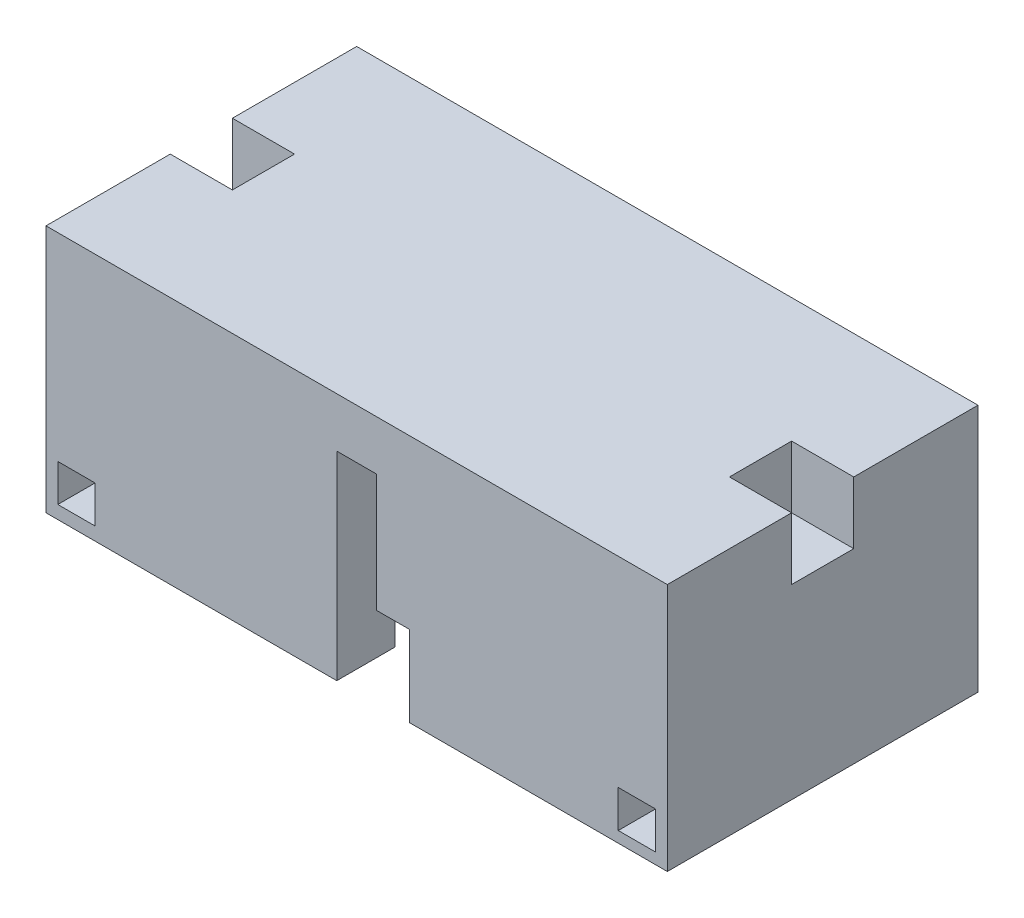
SolidWorks part; units mm, degrees
note: The reader was unsure of these and kept them because the rebuilt part matched: shared geometry of "Sketch34<3>", "Sketch34<4>".
ref_plane "Front Plane" through (0, 0, 0) normal (0, 0, 1) x (1, 0, 0)
ref_plane "Top Plane" through (0, 0, 0) normal (0, 1, 0) x (1, 0, 0)
ref_plane "Right Plane" through (0, 0, 0) normal (1, 0, 0) x (0, 0, -1)
sketch "Sketch1" plane through (0, 0, 0) normal (0, 1, 0) x (1, 0, 0)
  line L1 (-50, 50) -> (50, 50)
  line L2 (-50, 50) -> (-50, -50)
  line L3 (-50, -50) -> (50, -50)
  line L4 (50, 50) -> (50, -50)
  line L5 (-50, 50) -> (50, -50) construction
  line L6 (-50, -50) -> (50, 50) construction
  point P0 (0, 0)
  dimension "D1" = 100
  dimension "D2" = 100
extrude "Boss-Extrude1" add sketch "Sketch1" against normal blind 50
sketch "Sketch2" plane through (0, 0, 0) normal (0, 1, 0) x (1, 0, 0)
  line L0 (-50, -50) -> (50, -50)
  line L1 (50, -50) -> (50, 50)
  line L2 (50, 50) -> (-50, 50)
  line L3 (-50, 50) -> (-50, -50)
  line L4 (0, -50) -> (0, 0)
  line L5 (0, 0) -> (-50, 0)
  line L6 (0, 0) -> (50, 0)
  line L7 (-50, 0) -> (-50, -50)
  line L8 (50, 0) -> (50, -50)
  line L9 (-50, 0) -> (-50, 50)
  line L10 (50, 0) -> (50, 50)
  line L11 (0, 0) -> (0, 50)
ref_plane "BACK" through (0, -50, 0) normal (0, -1, 0) x (-1, 0, 0)
sketch "Sketch3" plane through (0, -50, 0) normal (0, -1, 0) x (-1, 0, 0)
  line L0 (-50, 50) -> (50, 50)
  line L1 (50, 50) -> (50, -50)
  line L2 (50, -50) -> (-50, -50)
  line L3 (-50, -50) -> (-50, 50)
  line L12 (-5, -20) -> (5, -20)
  line L13 (-5, -20) -> (-5, -30)
  line L14 (-5, -30) -> (5, -30)
  line L15 (5, -20) -> (5, -30)
  dimension "D1" = 10
  dimension "D2" = 10
sketch "Sketch4" plane through (0, 0, 0) normal (0, 1, 0) x (1, 0, 0)
  line L0 (0, -40) -> (0, -20)
  line L1 (5, -20) -> (-5, -20) construction
  circle A0 centre (0, 0) radius 40
  dimension "D1" = 80
ref_plane "Plane2" through (0, 0, 50) normal (0, 0, 1) x (1, 0, 0)
sketch "Sketch6" plane through (0, 0, 50) normal (0, 0, 1) x (1, 0, 0)
  line L0 (-50, 0) -> (-50, -150)
  line L1 (-50, 0) -> (50, 0)
  line L2 (50, 0) -> (50, -150)
  line L3 (50, -150) -> (-50, -150)
  line L4 (-50, -50) -> (50, -50)
  circle A0 centre (0, -150) radius 100
  dimension "D1" = 150
extrude "Boss-Extrude4" add sketch "Sketch6" against normal blind 50 separate body contours A0 L4 L0 | A0 L2 L4
ref_plane "Plane4" through (0, -63.3975, 0) normal (0, -1, 0) x (-1, 0, 0)
ref_plane "Plane5" through (0, 0, 0) normal (0, 0, -1) x (-1, 0, 0)
sketch "Sketch10" plane through (0, 0, 0) normal (0, 0, -1) x (-1, 0, 0)
  line L0 (50, -50) -> (50, -70)
  line L1 (50, -50) -> (-50, -50) construction
  line L2 (50, -50) -> (50, -63.3975) construction
  line L3 (50, -50) -> (30, -50)
  line L4 (-50, -50) -> (50, -50) construction
  line L5 (50, -70) -> (30, -50)
  line L6 (-68.5695, -50) -> (-48.5695, -50)
  line L7 (-55, -50) -> (55, -50) construction
  line L8 (-68.5695, -50) -> (-50, -57.4278)
  line L9 (-50, -50) -> (-50, -63.3975) construction
  line L10 (-48.5695, -50) -> (-50, -57.4278)
  dimension "D1" = 20
  dimension "D2" = 20
  dimension "D3" = 20
  dimension "D4" = 20
sketch "Sketch11" plane through (0, -63.3975, 0) normal (0, -1, 0) x (-1, 0, 0)
  line L0 (-50, -50) -> (-50, 0)
  line L1 (-50, 0) -> (50, 0)
  line L2 (50, 50) -> (50, -50) construction
  line L3 (50, 0) -> (50, -50)
  line L4 (50, -50) -> (-50, -50)
extrude "Cut-Extrude4" cut sketch "Sketch11" against normal blind 100
sketch "Sketch12" plane through (0, 0, 50) normal (0, 0, 1) x (1, 0, 0)
  line L0 (-50, -50) -> (-50, -30)
  line L1 (-50, -50) -> (-50, 0) construction
  line L2 (-50, -30) -> (-30, -30)
  line L3 (-30, -30) -> (-50, -50)
  line L4 (50, -50) -> (50, -30)
  line L5 (50, -50) -> (50, 0) construction
  line L6 (50, -30) -> (30, -30)
  line L7 (30, -30) -> (50, -50)
  dimension "D1" = 20
  dimension "D2" = 20
  dimension "D3" = 20
ref_plane "Plane6" through (0, 0, -50) normal (0, 0, -1) x (-1, 0, 0)
sketch "Sketch13" plane through (0, 0, -50) normal (0, 0, -1) x (-1, 0, 0)
  line L2 (50, -50) -> (50, -40)
  line L3 (50, -50) -> (50, -30) construction
  line L4 (50, -40) -> (-50, -40)
  line L5 (-50, -50) -> (-50, -30) construction
  line L6 (-50, -40) -> (-50, -50)
  line L7 (-50, -50) -> (50, -50)
extrude "Cut-Extrude5" cut sketch "Sketch13" against normal blind 50
sketch "Sketch14" plane through (0, -50, 0) normal (0, -1, 0) x (-1, 0, 0)
  line L0 (0, -50) -> (0, 0) construction
  line L1 (-5, -20) -> (5, -20)
  line L2 (-5, -20) -> (-5, -30)
  line L3 (-5, -30) -> (5, -30)
  line L4 (5, -20) -> (5, -30)
  line L5 (-5, -20) -> (5, -30) construction
  line L6 (-5, -30) -> (5, -20) construction
  line L8 (-4, -21) -> (4, -21)
  line L9 (-4, -21) -> (-4, -29)
  line L10 (-4, -29) -> (4, -29)
  line L11 (4, -21) -> (4, -29)
  line L12 (-4, -21) -> (4, -29) construction
  line L13 (-4, -29) -> (4, -21) construction
  point P0 (0, -25)
  point P8 (0, -25)
  dimension "D1" = 8
  dimension "D2" = 8
extrude "Cut-Extrude6" cut sketch "Sketch2" against normal blind 25 contours L5 L7 L0 L4 | L8 L6 L4 L0
sketch "Sketch18" plane through (0, 0, 0) normal (0, 0, -1) x (-1, 0, 0)
  line L0 (50, -50) -> (50, -70)
  line L1 (50, -70) -> (30, -50)
  line L2 (30, -50) -> (50, -50)
  line L3 (-50, -50) -> (-50, -69.5)
  line L4 (-50, -69.5) -> (-30.5, -50)
  line L5 (-50, -50) -> (50, -50) construction
  line L6 (-30.5, -50) -> (-50, -50)
  dimension "D1" = 45
extrude "Boss-Extrude5" add sketch "Sketch18" against normal blind 19.5
sketch "Sketch20" plane through (0, -40, 0) normal (0, -1, 0) x (1, 0, 0)
  line L0 (0, 0) -> (-30, 0)
  line L1 (-60.3987, 0) -> (60.3987, 0) construction
  line L2 (-30, 0) -> (-30, -22.9)
  line L3 (-30, -22.9) -> (-14, -22.9)
  line L4 (-14, -22.9) -> (-14, -27.9)
  line L5 (-14, -27.9) -> (-11.1, -27.9)
  line L6 (-11.1, -27.9) -> (-11.1, -22.9)
  line L7 (-30, -22.9) -> (-14, -22.9)
  line L8 (-7, -22.9) -> (-7, -14.9)
  line L9 (-7, -14.9) -> (-2.8, -14.9)
  line L10 (-2.8, -14.9) -> (3.2, -14.9)
  line L11 (3.2, -14.9) -> (3.2, 0)
  line L12 (3.2, 0) -> (0, 0)
  line L13 (-11.1, -22.9) -> (-7, -22.9)
  line L14 (3.2, 0) -> (-30, 0)
  line M4 (50, 0) -> (-50, 0)
extrude "Cut-Extrude7" cut sketch "Sketch20" against normal blind 12 contours L6 L13 L8 L9 L10 L11 L2 L3 L4 L5 M4
sketch "Sketch21" plane through (0, -40, 0) normal (0, -1, 0) x (1, 0, 0)
  line L0 (0, 0) -> (-3.2, 0)
  line L1 (-60.3987, 0) -> (60.3987, 0) construction
  line L2 (-3.2, 0) -> (-3.2, -14.9)
  line L3 (-7, -14.9) -> (3.2, -14.9) construction
  line L4 (-3.2, -14.9) -> (3.2, -14.9)
  line L5 (3.2, -14.9) -> (3.2, 0)
  line L6 (3.2, -14.9) -> (3.2, 0) construction
  line L7 (3.2, 0) -> (-3.2, 0)
  line M8 (3.2, 0) -> (3.2, -14.9)
  line M9 (3.2, -14.9) -> (-7, -14.9)
extrude "Cut-Extrude8" cut sketch "Sketch21" against normal blind 32 contours L7 L0 L2 M8 M9
ref_plane "Plane7" through (0, 0, 0) normal (0, 0, -1) x (-1, 0, 0)
sketch "Sketch27" plane through (0, 0, 0) normal (0, 0, -1) x (-1, 0, 0)
  line L0 (-5, -50) -> (-5, -40)
  line L1 (-5, -50) -> (5, -50) construction
  line L2 (50, -40) -> (-50, -40) construction
  line L3 (-5, -40) -> (-3.2, -40)
  line L4 (-3.2, -50) -> (-3.2, -18)
  line L5 (-3.2, -18) -> (3.2, -18)
  line L6 (3.2, -18) -> (3.2, -50)
  line L7 (3.2, -50) -> (-3.2, -50)
extrude "Cut-Extrude9" cut sketch "Sketch27" against normal blind 29 contours L7 L6 L5 L4
sketch "Sketch28" plane through (0, -25, 0) normal (0, 1, 0) x (1, 0, 0)
  line L0 (0, -25) -> (0, -10)
  line L1 (-7.5, -17.5) -> (7.5, -17.5)
  line L2 (-7.5, -17.5) -> (-7.5, -32.5)
  line L3 (-7.5, -32.5) -> (7.5, -32.5)
  line L4 (7.5, -17.5) -> (7.5, -32.5)
  line L5 (-7.5, -17.5) -> (7.5, -32.5) construction
  line L6 (-7.5, -32.5) -> (7.5, -17.5) construction
  point P0 (0, -25)
  dimension "D1" = 15
  dimension "D2" = 15
sketch "Sketch29" plane through (0, 0, -50) normal (0, 0, -1) x (-1, 0, 0)
  line L0 (0, -40) -> (30, -40)
  line L1 (50, -40) -> (-50, -40) construction
  line L2 (30, -40) -> (30, -28)
  line L3 (30, -28) -> (0, -28)
  line L4 (0, -28) -> (0, -40)
  line L5 (24, -36.5) -> (24, -40)
  line L6 (24, -34) -> (24, -36.5)
  line L7 (24, -34) -> (24, -31.5)
  line L8 (24, -31.5) -> (30, -31.5)
  line L9 (24, -36.5) -> (30, -36.5)
  line L10 (24, -40) -> (30, -40)
  line L11 (30, -36.5) -> (24, -36.5)
extrude "Cut-Extrude10" cut sketch "Sketch29" against normal blind 28 contours L6 L9 L2 L8 L7 | L9 L5 L0 L2
sketch "Sketch30" plane through (0, -25, 0) normal (0, 1, 0) x (1, 0, 0)
  line L0 (-50, -50) -> (-50, 0)
  line L1 (-50, 50) -> (-50, -50) construction
  line L2 (-50, 0) -> (50, 0)
  line L3 (50, -50) -> (50, 50) construction
  line L4 (50, 0) -> (50, -50)
  line L5 (50, -50) -> (-50, -50)
sketch "Sketch31" plane through (-50, 0, 0) normal (-1, 0, 0) x (0, 0, 1)
  line L0 (0, -50) -> (0, -40)
  line L1 (-50, -50) -> (50, -50) construction
  line L2 (0, 60.3987) -> (0, -60.3987) construction
  line L3 (0, 36.7438) -> (0, -36.7438) construction
extrude "Cut-Extrude11" cut sketch "Sketch30" against normal blind 45
sketch "Sketch32" plane through (0, 0, 0) normal (0, 0, 1) x (1, 0, 0)
  line L0 (-50, -40) -> (-50, -30.2)
  line L1 (-50, -50) -> (-50, -30) construction
  line L2 (-50, -40) -> (-50, 0) construction
  line L3 (-50, -30.2) -> (-40.2, -30.2)
  line L4 (-40.2, -30.2) -> (-40.2, -40)
  line L5 (-50, -40) -> (-30, -40) construction
  line L6 (-40.2, -40) -> (-50, -40)
  line L7 (50, -40) -> (50, -30.2)
  line L8 (50, -50) -> (50, -30) construction
  line L9 (50, -40) -> (50, 0) construction
  line L10 (50, -30.2) -> (40.2, -30.2)
  line L11 (40.2, -30.2) -> (40.2, -40)
  line L12 (3.2, -40) -> (50, -40) construction
  line L13 (40.2, -40) -> (50, -40)
extrude "Boss-Extrude6" add sketch "Sketch32" along normal blind 9.8
chamfer "Chamfer1" distance 1 angle 45 6 edges at (40.2, -35.1, 9.8) (40.2, -30.2, 4.9) (-40.2, -35.1, 9.8) (-40.2, -30.2, 4.9) (40.2, -40, 4.9) (-40.2, -40, 4.9)
sketch "Sketch34" plane through (0, -40, 0) normal (0, -1, 0) x (1, 0, 0)
  line L0 (-11.1, -27.9) -> (-11.1, -22.9)
  line L1 (-11.1, -22.9) -> (-7, -22.9)
  line L2 (-7, -22.9) -> (-7, -14.9)
  line L3 (-7, -14.9) -> (3.2, -14.9)
  line L4 (3.2, -14.9) -> (3.2, 0)
  line L5 (-60.3987, 0) -> (60.3987, 0) construction
  line L6 (3.2, 0) -> (3.2, -14.9) construction
  line L7 (3.2, 0) -> (-30, 0)
  line L8 (-30, 0) -> (-30, -50) construction
  line L9 (-50, 0) -> (-30, 0) construction
  line L10 (-30, 0) -> (-30, -22.9)
  line L11 (-30, -22.9) -> (-14, -22.9)
  line L12 (-14, -22.9) -> (-14, -27.9)
  line L13 (-14, -27.9) -> (-11.1, -27.9)
  line L14 (-30, 0) -> (-30.5, 0)
  line L15 (-30.5, 0) -> (-30.5, -22.9)
  line L16 (-30, -22.9) -> (-30.5, -22.9)
  line L17 (-30.5, -22.9) -> (-30.5, -33.4)
  line L18 (-30.5, -33.4) -> (-14.5, -33.4)
  line L19 (-14.5, -33.4) -> (-14.5, -38.9)
  line L20 (-14.5, -38.9) -> (-10.6, -38.9)
  line L21 (-10.6, -38.9) -> (-10.6, -33.4)
  line L22 (-10.6, -33.4) -> (-6.5, -33.4)
  line L23 (-6.5, -33.4) -> (-6.5, -24.9)
  line L24 (-6.5, -24.9) -> (8.5, -24.9)
  line L25 (-30.5, -33.4) -> (-30.5, -9.4)
  line L26 (-30.5, -9.4) -> (-14.5, -9.4)
  line L27 (-14.5, -9.4) -> (-14.5, -3.9)
  line L28 (-14.5, -3.9) -> (-10.6, -3.9)
  line L29 (-10.6, -3.9) -> (-10.6, -9.4)
  line L30 (-10.6, -9.4) -> (-3.2, -9.4)
  line L31 (-3.2, 0) -> (-3.2, -14.9) construction
  line L32 (8.5, -24.9) -> (8.5, 0)
  line L33 (8.5, 0) -> (3.2, 0)
  line L34 (3.2, -24.9) -> (3.2, 0)
  line L35 (3.2, 0) -> (8.5, 0)
  line L36 (3.2, -24.9) -> (8.5, -24.9)
  line L37 (-3.2, -9.4) -> (3.2, -9.4)
  line L38 (3.2, -9.4) -> (3.2, -24.9)
  line L39 (-3.2, -9.4) -> (-3.2, 0)
  line L40 (3.2, -24.9) -> (3.2, -33.4)
  line L41 (3.2, -33.4) -> (-6.5, -33.4)
  line L42 (-30.5, -33.4) -> (-30.5, -50)
  line L43 (50, -50) -> (-50, -50) construction
  line L44 (-30.5, -50) -> (-30, -50)
  line L45 (-30, 0) -> (-30, -50) construction
  line L46 (-30, -50) -> (-30, -33.4)
  line L47 (-30, -22.9) -> (-30, -50) construction
  line L48 (-30, -50) -> (-24, -50)
  line L49 (-24, -22.9) -> (-24, -50) construction
  line L50 (-24, -50) -> (-24, -33.4)
  line L51 (-24, -22.9) -> (-24, -50) construction
  line L52 (8.5, -24.9) -> (8.5, -50)
  line L53 (8.5, -50) -> (3.2, -50)
  line L54 (3.2, -50) -> (3.2, -24.9)
  line M18 (40.2, 0) -> (3.2, 0)
  line M19 (3.2, 0) -> (3.2, -14.9)
  line M20 (3.2, -14.9) -> (-7, -14.9)
  line M21 (-7, -14.9) -> (-7, -22.9)
  line M22 (-7, -22.9) -> (-11.1, -22.9)
  line M23 (-11.1, -22.9) -> (-11.1, -27.9)
  line M24 (-11.1, -27.9) -> (-14, -27.9)
  line M25 (-14, -27.9) -> (-14, -22.9)
  line M26 (-14, -22.9) -> (-24, -22.9)
  line M67 (-24, -22.9) -> (-24, -50)
  line M68 (-24, -50) -> (50, -50)
extrude "Boss-Extrude7" add sketch "Sketch34" against normal blind 13 contours L30 L39 L7 L10 L26 L27 L28 L29
extrude "Cut-Extrude12" cut sketch "Sketch34<3>" against normal blind 13 contours L34 L24 L32 M18 M19 | L37 L30 L29 L28 L27 L26 L10 L11 L34 M26 M25 M24 M23 M22 M21 M20 | L24 L34 L18 L19 L20 L21 L22 L23 M20 M21 M22 M23 M24 M25 M26 M67 | L41 L40 L24 L23 | L17 L18 L11 L16 M67 | L26 L15 L16 L10 | L44 L46 L18 L42 | L46 L48 L18 M67
sketch "Sketch34<3>" plane through (0, -40, 0) normal (0, -1, 0) x (1, 0, 0) same geometry as "Sketch34"
sketch "Sketch36" plane through (0, 0, 0) normal (0, 1, 0) x (1, 0, 0)
  line L0 (50, 50) -> (50, 0)
  line L1 (50, -50) -> (50, 50) construction
  line L2 (-50, 50) -> (-50, 20)
  line L3 (40, 25) -> (40, 30)
  line L4 (40, 25) -> (40, 20)
  line L5 (40, 20) -> (50, 20)
  line L6 (40, 30) -> (50, 30)
  line L7 (-50, 50) -> (-50, -50) construction
  line L8 (-50, 20) -> (-40, 20)
  line L9 (-40, 20) -> (-40, 30)
  line L10 (-40, 30) -> (-50, 30)
  line L11 (-50, 20) -> (-50, 0)
  line L12 (-50, 0) -> (50, 0)
  line L13 (50, 50) -> (-50, 50)
extrude "Cut-Extrude13" cut sketch "Sketch36" against normal blind 10 and the other way through all contours L9 L10 L2 L8 | L6 L3 L4 L5 L0
sketch "Sketch37" plane through (0, -40, 0) normal (0, -1, 0) x (1, 0, 0)
  line L0 (-50, 0) -> (-50, 9.8)
  line L1 (-50, -50) -> (-50, 50) construction
  line L2 (-50, 9.8) -> (-40.2, 9.8)
  line L3 (-40.2, 9.8) -> (-40.2, 0)
  line L4 (-50, 0) -> (-30, 0) construction
  line L5 (-40.2, 0) -> (-50, 0)
  line L6 (50, 0) -> (40.2, 0)
  line L7 (50, 50) -> (50, -50) construction
  line L8 (-60.3987, 0) -> (60.3987, 0) construction
  line L9 (40.2, 8.8) -> (40.2, 0) construction
  line L10 (40.2, 0) -> (40.2, 10.0488)
  line L11 (40.2, 10.0488) -> (50, 10.0488)
  line L12 (50, 10.0488) -> (50, 0)
extrude "Cut-Extrude15" cut sketch "Sketch37" against normal blind 10
sketch "Sketch38" plane through (0, 0, 0) normal (0, 0, 1) x (1, 0, 0)
  line L0 (-50, -40) -> (-40.2, -40)
  line L1 (-50, -40) -> (-3.2, -40) construction
  line L2 (-40.2, -40) -> (-40.2, -30.2)
  line L3 (-40.2, -30.2) -> (-50, -30.2)
  line L4 (-50, -50) -> (-50, -30) construction
  line L5 (-50, -30.2) -> (-50, -40)
  line L6 (-45.1, -40) -> (-45.1, -34.8905)
  line L7 (50, -40) -> (40.2, -40)
  line L8 (-48.1, -31.8905) -> (-42.1, -31.8905)
  line L9 (-48.1, -31.8905) -> (-48.1, -37.8905)
  line L10 (-48.1, -37.8905) -> (-42.1, -37.8905)
  line L11 (-42.1, -31.8905) -> (-42.1, -37.8905)
  line L12 (-48.1, -31.8905) -> (-42.1, -37.8905) construction
  line L13 (-48.1, -37.8905) -> (-42.1, -31.8905) construction
  line L14 (50, -50) -> (50, -30) construction
  line L15 (8.5, -40) -> (50, -40) construction
  line L16 (40.2, -40) -> (40.2, -30.2)
  line L17 (40.2, -30.2) -> (50, -30.2)
  line L18 (50, -30.2) -> (50, -40)
  line L19 (45.1, -40) -> (45.1, -35.2309)
  line L21 (42.1, -32.2309) -> (48.1, -32.2309)
  line L22 (42.1, -32.2309) -> (42.1, -38.2309)
  line L23 (42.1, -38.2309) -> (48.1, -38.2309)
  line L24 (48.1, -32.2309) -> (48.1, -38.2309)
  line L25 (42.1, -32.2309) -> (48.1, -38.2309) construction
  line L26 (42.1, -38.2309) -> (48.1, -32.2309) construction
  dimension "D1" = 6
  dimension "D2" = 6
  dimension "D3" = 6
  dimension "D4" = 6
  dimension "D5" = 9.8
  dimension "D6" = 9.8
  dimension "D7" = 9.8
  dimension "D8" = 9.8
extrude "Cut-Extrude16" cut sketch "Sketch38" against normal blind 6
sketch "Sketch39" plane through (0, -40, 0) normal (0, -1, 0) x (1, 0, 0)
  line L0 (-3.2, -14.9) -> (-3.2, -33.4)
  line L1 (-10.6, -33.4) -> (3.2, -33.4) construction
  line L2 (-3.2, -33.4) -> (3.2, -33.4)
  line L3 (3.2, -33.4) -> (3.2, -14.9)
  line L4 (3.2, -14.9) -> (-3.2, -14.9)
  line L5 (-3.2, -33.4) -> (-3.2, -50)
  line L6 (3.2, -33.4) -> (3.2, -50)
  line L9 (50, -50) -> (-50, -50) construction
  line L10 (-3.2, -50) -> (3.2, -50)
  line M5 (3.2, -24.9) -> (3.2, -33.4)
  line M6 (3.2, -33.4) -> (-10.6, -33.4)
  line M12 (-24, -50) -> (50, -50)
extrude "Cut-Extrude17" cut sketch "Sketch39" against normal blind 32 contours L6 L5 M6 M12 | L3 L4 L0 M6 M5
extrude "Cut-Extrude18" cut sketch "Sketch34<4>" against normal blind 13 contours L54 L52 L24 L40 M68
sketch "Sketch34<4>" plane through (0, -40, 0) normal (0, -1, 0) x (1, 0, 0) same geometry as "Sketch34"
